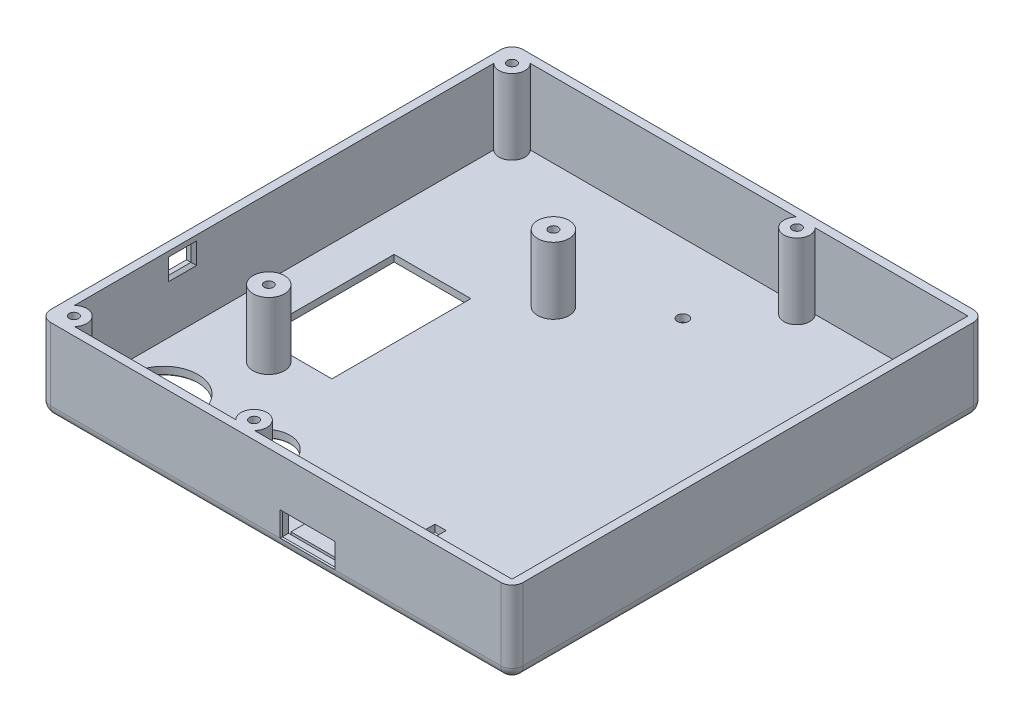
SolidWorks part; units mm, degrees
ref_plane "前视基准面" through (0, 0, 0) normal (0, 0, 1) x (1, 0, 0)
ref_plane "上视基准面" through (0, 0, 0) normal (0, 1, 0) x (1, 0, 0)
ref_plane "右视基准面" through (0, 0, 0) normal (1, 0, 0) x (0, 0, -1)
sketch "草图1" plane through (0, 0, 0) normal (0, 1, 0) x (1, 0, 0)
  line L1 (-42.5, 42.5) -> (42.5, 42.5)
  line L2 (-42.5, 42.5) -> (-42.5, -42.5)
  line L3 (-42.5, -42.5) -> (42.5, -42.5)
  line L4 (42.5, 42.5) -> (42.5, -42.5)
  line L5 (-42.5, 42.5) -> (42.5, -42.5) construction
  line L6 (-42.5, -42.5) -> (42.5, 42.5) construction
  point P0 (0, 0)
  dimension "D1" = 85
  dimension "D2" = 85
extrude "凸台-拉伸1" add sketch "草图1" along normal blind 15
shell "抽壳1" thickness 1.5 removed face at (0, 15, 0)
fillet "圆角1" radius 2 4 edges at (0, 0, 42.5) (-42.5, 0, 0) (42.5, 0, 0) (0, 0, -42.5)
fillet "圆角2" radius 2 8 edges at (-41.9142, 0.5858, -41.9142) (-41.9142, 0.5858, 41.9142) (41.9142, 0.5858, 41.9142) (41.9142, 0.5858, -41.9142) (-42.5, 8.5, -42.5) (-42.5, 8.5, 42.5) (42.5, 8.5, 42.5) (42.5, 8.5, -42.5)
sketch "草图16" plane through (0, 0, 42.5) normal (0, 0, 1) x (1, 0, 0)
  line L1 (1, 2.25) -> (10.5, 2.25)
  line L2 (1, 2.25) -> (1, 6.25)
  line L3 (1, 6.25) -> (10.5, 6.25)
  line L4 (10.5, 2.25) -> (10.5, 6.25)
  line L7 (10.25, 3) -> (10.25, 7) construction
  line L8 (1.25, 3) -> (1.25, 7) construction
  line L9 (10.25, 6) -> (1.25, 6) construction
  line L10 (9.75, 2.5) -> (1.75, 2.5) construction
  dimension "D1" = 0.25
  dimension "D2" = 0.25
  dimension "D3" = 0.25
  dimension "D4" = 0.25
extrude "充电口切除-拉伸7" cut sketch "草图16" against normal up to next
sketch "草图3" plane through (0, 0, 0) normal (0, -1, 0) x (1, 0, 0)
  line L1 (12, 25.85) -> (14, 25.85)
  line L2 (12, 25.85) -> (12, 33.85)
  line L3 (12, 33.85) -> (14, 33.85)
  line L4 (14, 25.85) -> (14, 33.85)
  line L7 (13, 31.2) -> (13, 28.5) construction
  line L8 (12.5, 31.2) -> (13.5, 31.2) construction
  line L9 (13.5, 28.5) -> (12.5, 28.5) construction
  line L10 (13, 29.85) -> (11.5693, 29.85) construction
  dimension "D1" = 2
  dimension "D2" = 8
extrude "充电灯切除-拉伸2" cut sketch "草图3" against normal up to next
sketch "草图4" plane through (0, 0, 0) normal (0, -1, 0) x (1, 0, 0)
  circle A2 centre (-32.65, 30) radius 6.15
  circle A3 centre (-32.65, 30) radius 5.85 construction
  circle A4 centre (-32.65, 30) radius 5.85 construction
extrude "按钮切除-拉伸3" cut sketch "草图4" against normal up to next
chamfer "充电口灯倒角1" distance 0.2 angle 45 12 edges at (13, 0, 33.85) (14, 0, 29.85) (12, 0, 29.85) (13, 0, 25.85) (10.5, 4.25, 41) (5.75, 2.25, 41) (5.75, 6.25, 41) (1, 4.25, 41) (10.5, 4.25, 42.5) (5.75, 2.25, 42.5) (5.75, 6.25, 42.5) (1, 4.25, 42.5)
sketch "草图5" plane through (-42.5, 0, 0) normal (-1, 0, 0) x (0, 0, 1)
  line L1 (16.25, 13.57) -> (20.25, 13.57)
  line L2 (16.25, 13.57) -> (16.25, 10.73)
  line L3 (16.25, 10.73) -> (20.25, 10.73)
  line L4 (20.25, 13.57) -> (20.25, 10.73)
  line L5 (18.25, 12.57) -> (16.45, 12.57) construction
  line L6 (18.25, 10.93) -> (20.05, 10.93) construction
  line L8 (20.05, 10.93) -> (20.05, 12.57) construction
  line L9 (16.45, 12.57) -> (16.45, 10.93) construction
  dimension "D1" = 0.2
  dimension "D2" = 1
  dimension "D3" = 0.2
  dimension "D4" = 0.2
extrude "开关切除-拉伸4" cut sketch "草图5" against normal up to next
chamfer "开关倒角3" distance 0.2 angle 45 4 edges at (-42.5, 12.15, 20.25) (-42.5, 10.73, 18.25) (-42.5, 12.15, 16.25) (-42.5, 13.57, 18.25)
chamfer "开关倒角4" distance 0.5 angle 45 4 edges at (-41, 12.15, 20.25) (-41, 10.73, 18.25) (-41, 12.15, 16.25) (-41, 13.57, 18.25)
sketch "草图6" plane through (0, 0, 0) normal (0, -1, 0) x (1, 0, 0)
  line L5 (-19.9, 12.5) -> (-33.7, 12.5)
  line L6 (-33.7, 12.5) -> (-33.7, -12.5)
  line L7 (-19.9, -12.5) -> (-33.7, -12.5)
  line L8 (-19.9, 12.5) -> (-19.9, -12.5)
  line L9 (40.5, 40.5) -> (-40.5, 40.5) construction
  line L10 (-40.5, 40.5) -> (-40.5, -40.5) construction
  dimension "D1" = 13.8
  dimension "D2" = 25
  dimension "D3" = 28
  dimension "D4" = 6.8
extrude "屏幕切除-拉伸6" cut sketch "草图6" against normal up to next
chamfer "屏幕倒角6" distance 0.3 angle 45 4 edges at (-26.8, 0, 12.5) (-33.7, 0, 0) (-26.8, 0, -12.5) (-19.9, 0, 0)
sketch "草图7" plane through (0, 0, 0) normal (0, -1, 0) x (1, 0, 0)
  line L4 (40.5, 40.5) -> (-40.5, 40.5)
  line L6 (40.5, 40.5) -> (-40.5, 40.5)
  line L8 (-40.5, 40.5) -> (-40.5, -40.5)
  line L10 (-40.5, 40.5) -> (-40.5, -40.5)
  line L12 (-40.5, -40.5) -> (40.5, -40.5)
  line L13 (-40.5, -40.5) -> (40.5, -40.5)
  line L14 (40.5, -40.5) -> (40.5, 40.5)
  line L15 (40.5, -40.5) -> (40.5, 40.5)
  circle A0 centre (-14.8774, 29.5) radius 4.25 construction
  circle A1 centre (-14.8774, 29.5) radius 4.25 construction
  circle A3 centre (-14.8774, 29.5) radius 4.45
  dimension "D1" = 0
extrude "人体切除-拉伸7" cut sketch "草图7" against normal up to next contours A3
sketch "草图9" plane through (0, 0, 0) normal (0, -1, 0) x (1, 0, 0)
  circle A0 centre (2.2382, -28.5) radius 1
extrude "蜂鸣切除-拉伸8" cut sketch "草图9" against normal up to next
chamfer "蜂鸣倒角7" distance 0.2 angle 45 3 edges at (2.2382, 0, -29.5) (-32.65, 0, 23.85) (-14.8774, 0, 25.05)
sketch "草图10" plane through (0, 1.5, 0) normal (0, 1, 0) x (1, 0, 0)
  line L0 (41, 41) -> (-41, 41) construction
  line L1 (-41, 41) -> (-41, -41) construction
  line L2 (-41, -41) -> (41, -41) construction
  line L4 (-3, -41) -> (-3, -13) construction
  line L6 (-41, -41) -> (41, -41) construction
  line L8 (8.85, 37.5) -> (8.85, 36.5) construction
  circle A0 centre (-39.4, 39.4) radius 0.825
  circle A1 centre (-39.4, -39.4) radius 0.825
  circle A2 centre (-7, -39.4) radius 0.825
  circle A3 centre (11.85, 39.4) radius 0.825
  dimension "D1" = 1.65
  dimension "D6" = 3
  dimension "D2" = 1.6
  dimension "D3" = 1.6
  dimension "D4" = 1.6
  dimension "D5" = 1.6
  dimension "D7" = 1.6
  dimension "D8" = 4
  dimension "D9" = 1.6
extrude "四角固定拉伸-薄壁1" add sketch "草图10" along normal up to surface (13.5 mm away) thin thin type one direction wall 1.5
sketch "草图12" plane through (0, 1.5, 0) normal (0, 1, 0) x (1, 0, 0)
  line L1 (-12, -12.5) -> (-39, -12.5) construction
  line L2 (-24.75, -14.5) -> (-24.75, -19.5) construction
  line L3 (-8.25, 31) -> (-8.25, -15.5) construction
  line L5 (-8.75, 21.7) -> (-37.15, 21.7) construction
  circle A0 centre (-28.25, -15.5) radius 2.825
  circle A1 centre (-11.25, 18.7) radius 2.825
  circle A2 centre (-28.25, -15.5) radius 0.825
  circle A3 centre (-11.25, 18.7) radius 0.825
  dimension "D1" = 2
  dimension "D4" = 2
  dimension "D7" = 1.65
  dimension "D8" = 1.65
  dimension "D2" = 3
  dimension "D3" = 3.5
  dimension "D5" = 3
  dimension "D6" = 3
extrude "压板固定凸台-拉伸2" add sketch "草图12" along normal up to surface (12 mm away)
sketch "草图14" plane through (42.5, 0, 0) normal (1, 0, 0) x (0, 0, -1)
  line L0 (40.5, 0) -> (-40.5, 0) construction
  line L1 (10, 0) -> (15, 0)
  line L2 (10, 0) -> (10, 5)
  line L3 (10, 5) -> (15, 5)
  line L4 (15, 0) -> (15, 5)
  line L5 (0, 0) -> (0, 15) construction
  line L6 (-40.5, 15) -> (40.5, 15) construction
  line L7 (-15, 0) -> (-15, 5)
  line L8 (-10, 5) -> (-15, 5)
  line L9 (-10, 0) -> (-10, 5)
  line L10 (-10, 0) -> (-15, 0)
  dimension "D1" = 5
  dimension "D2" = 5
  dimension "D3" = 10
extrude "电池顶凸台-拉伸3" add sketch "草图14" against normal blind 3.9 from surface starting at face at (41, 8.25, 0)
sketch "草图15" plane through (0, 1.5, 0) normal (0, 1, 0) x (1, 0, 0)
  line L1 (1.25, -41) -> (10.25, -41)
  line L2 (1.25, -41) -> (1.25, -37)
  line L3 (1.25, -37) -> (10.25, -37)
  line L4 (10.25, -41) -> (10.25, -37)
extrude "充电板凸台-拉伸4" add sketch "草图15" along normal up to surface (1 mm away)
